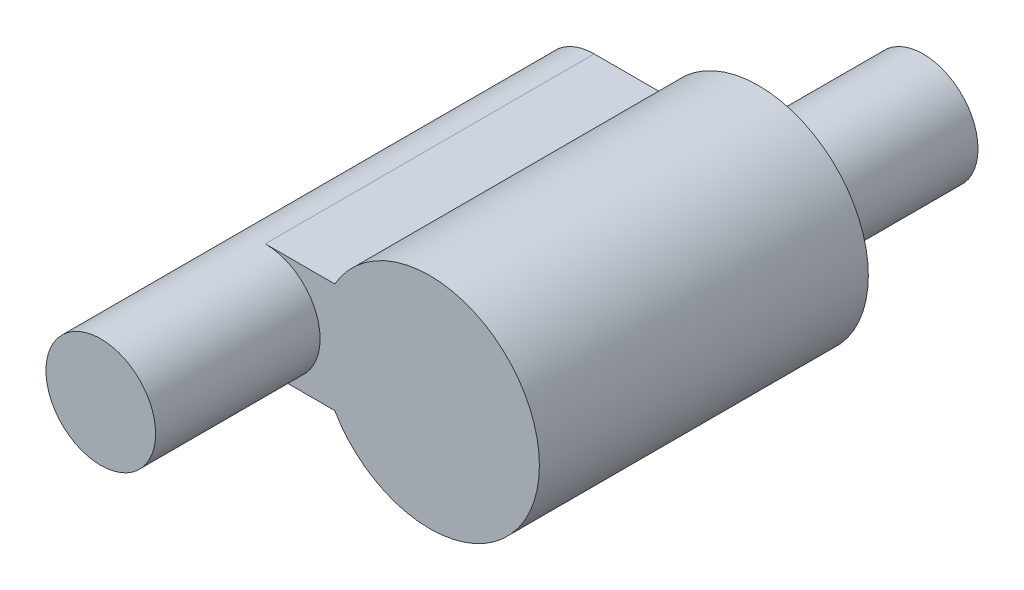
SolidWorks part; units mm, degrees
ref_plane "Спереди" through (0, 0, 0) normal (0, 0, 1) x (1, 0, 0)
ref_plane "Сверху" through (0, 0, 0) normal (0, 1, 0) x (1, 0, 0)
ref_plane "Справа" through (0, 0, 0) normal (1, 0, 0) x (0, 0, -1)
other "Configuration Table"
sketch "Sketch1" plane through (0, 0, 0) normal (0, 0, 1) x (1, 0, 0)
  line L0 (6.2799, 7.8479) -> (-8.0198, 7.8479) construction
  line L1 (-6.8342, 8.8479) -> (-5.5663, 8.8479)
  line L2 (-6.8342, 6.8479) -> (-5.5663, 6.8479)
  arc A0 (-6.8342, 8.8479) -> (-6.8342, 6.8479) centre (-6.8342, 7.8479) ccw
  arc A1 (-5.5663, 6.8479) -> (-5.5663, 8.8479) centre (-3.8342, 7.8479) ccw
  arc A2 (-6.8342, 6.8479) -> (-5.8342, 7.8479) centre (-6.8342, 7.8479) ccw construction
  arc A3 (-5.8342, 7.8479) -> (-6.8342, 8.8479) centre (-6.8342, 7.8479) ccw construction
  arc A4 (-5.5663, 6.8479) -> (-5.8342, 7.8479) centre (-3.8342, 7.8479) cw construction
  arc A5 (-5.8342, 7.8479) -> (-5.5663, 8.8479) centre (-3.8342, 7.8479) cw construction
  dimension "D1" = 2
  dimension "D3" = 4
  dimension "D2" = 2
  dimension "D4" = 3
extrude "Boss-Extrude1" add sketch "Sketch1" along normal blind 6 contours A0 | A1 L1 | A1 A0 | A1 L1 A0 | A1 A0 | L1 A1 A0 | A0 A1 | L1 A1 L2 A0 region at (-4.491, 7.8479, 0)
ref_plane "Plane1" through (0, 0, 6) normal (0, 0, 1) x (1, 0, 0)
sketch "Sketch2" plane through (0, 0, 6) normal (0, 0, 1) x (1, 0, 0)
  circle A0 centre (-6.8342, 7.8479) radius 1
  arc A1 (-6.8342, 8.8479) -> (-6.8342, 6.8479) centre (-6.8342, 7.8479) ccw construction
extrude "Boss-Extrude2" add sketch "Sketch2" along normal blind 3
ref_plane "Plane2" through (0, 0, 0) normal (0, 0, -1) x (-1, 0, 0)
sketch "Sketch3" plane through (0, 0, 0) normal (0, 0, -1) x (-1, 0, 0)
  circle A0 centre (3.8342, 7.8479) radius 1
  circle A1 centre (6.8342, 7.8479) radius 1 construction
extrude "Boss-Extrude3" add sketch "Sketch3" along normal blind 3
equation "\"R small\"= 2"
equation "\"R big\"= 4"
equation "\"width\"= 0.6"
equation "\"border width\"= 1"
equation "\"D3@Sketch1\"=\"R big\""
equation "\"D2@Sketch1\"=\"R small\""
equation "\"D1@Sketch1\"=\"R small\""
equation "\"depth\"= 3"
